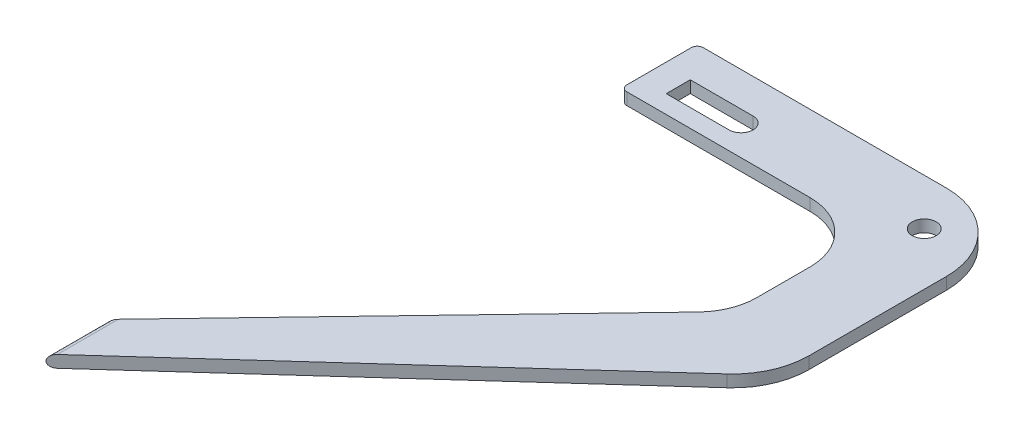
SolidWorks part; units mm, degrees
ref_plane "Front Plane" through (0, 0, 0) normal (0, 0, 1) x (1, 0, 0)
ref_plane "Top Plane" through (0, 0, 0) normal (0, 1, 0) x (1, 0, 0)
ref_plane "Right Plane" through (0, 0, 0) normal (1, 0, 0) x (0, 0, -1)
sketch "Sketch1" plane through (0, 0, 0) normal (0, 1, 0) x (1, 0, 0)
  line L0 (0, 48.4129) -> (0, 37.692)
  line L1 (1, 36.692) -> (31.48, 36.692)
  line L2 (15, 41.7006) -> (15, -54.6067) construction
  line L3 (-9.52, -49.4391) -> (-9.52, -39.4391)
  line L4 (-9.52, -49.4391) -> (50.0114, 4.3857)
  line L5 (54.2008, 13.8216) -> (54.2008, 36.692)
  line L6 (1, 49.4129) -> (41.48, 49.4129)
  line L7 (-9.52, -39.4391) -> (38.7027, 10.9212)
  line L8 (41.48, 17.8373) -> (41.48, 26.692)
  line L9 (15, 43.7006) -> (4.5495, 43.7006)
  line L10 (4.5495, 43.7006) -> (4.5495, 39.7006)
  line L11 (4.5495, 39.7006) -> (15, 39.7006)
  arc A0 (41.48, 17.8373) -> (38.7027, 10.9212) centre (31.48, 17.8373) cw
  arc A1 (41.48, 26.692) -> (31.48, 36.692) centre (31.48, 26.692) ccw
  arc A2 (50.0114, 4.3857) -> (54.2008, 13.8216) centre (41.48, 13.8216) ccw
  arc A3 (54.2008, 36.692) -> (41.48, 49.4129) centre (41.48, 36.692) ccw
  arc A4 (1, 36.692) -> (0, 37.692) centre (1, 37.692) cw
  arc A5 (1, 49.4129) -> (0, 48.4129) centre (1, 48.4129) ccw
  arc A6 (15, 39.7006) -> (15, 43.7006) centre (15, 41.7006) ccw
  circle A7 centre (45.48, 41.7006) radius 2
  point P9 (36, 36.692)
  point P18 (0, 36.692)
  point P21 (0, 49.4129)
  dimension "D4" = 24.52
  dimension "D5" = 40.48
  dimension "D7" = 1
  dimension "D8" = 15
  dimension "D10" = 4
  dimension "D2" = 10
  dimension "D3" = 10
  dimension "D11" = 30.48
extrude "Boss-Extrude2" add sketch "Sketch1" along normal blind 2
fillet "Fillet1" radius 1 1 edges at (-9.52, 2, 44.4391) type face fillet first side face at (45.48, 2, -39.7006) second side face at (-9.52, 1, 44.4391)
fillet "Fillet2" radius 1 1 edges at (-9.52, 0, 44.4391) type face fillet first side face at (-9.52, 0.5, 44.4391) second side face at (45.48, 0, -39.7006)
